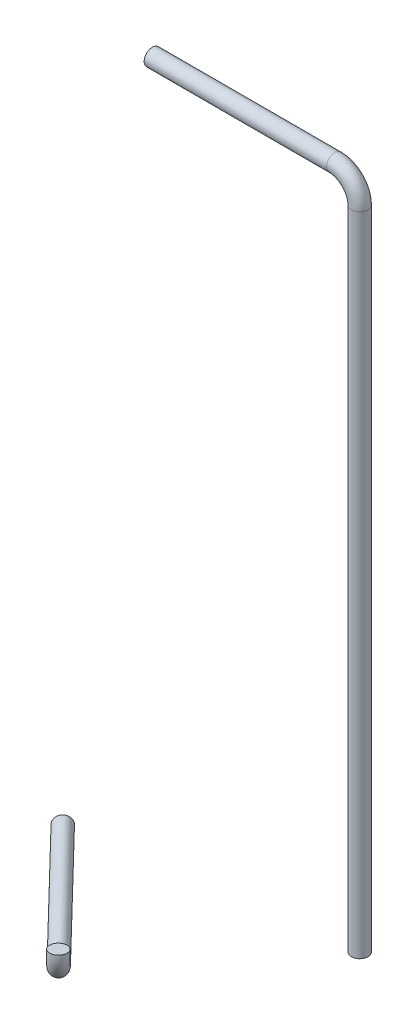
SolidWorks part; units mm, degrees
ref_plane "Front Plane" through (0, 0, 0) normal (0, 0, 1) x (1, 0, 0)
ref_plane "Top Plane" through (0, 0, 0) normal (0, 1, 0) x (1, 0, 0)
ref_plane "Right Plane" through (0, 0, 0) normal (1, 0, 0) x (0, 0, -1)
sketch "Sketch1" plane through (0, 0, 0) normal (0, 0, 1) x (1, 0, 0)
  line L0 (0, 0) -> (22, 0)
  line L1 (25, -3) -> (25, -81.02)
  arc A0 (22, 0) -> (25, -3) centre (22, -3) cw
  point P6 (25, 0)
  dimension "D3" = 3
  dimension "D1" = 25
  dimension "D2" = 81.02
sketch "Sketch3" plane through (0, 0, 0) normal (1, 0, 0) x (0, 0, -1)
  circle A0 centre (0, 0) radius 1
  dimension "D1" = 2
sweep "Sweep1" add profiles "Sketch3" path "Sketch1"
ref_plane "Plane2" through (-3.5863, 0, 3.4697) normal (0.7187, 0, -0.6953) x (-0.6953, 0, -0.7187)
ref_axis "Axis1" through (0, 0, 0) along (1, 0, 0)
ref_plane "Plane3" through (-5.5628, 0, 5.3818) normal (0.7187, 0, -0.6953) x (-0.6953, 0, -0.7187)
sketch "Sketch4" plane through (-5.5628, 0, 5.3818) normal (0.7187, 0, -0.6953) x (-0.6953, 0, -0.7187)
  line L4 (-14.3921, -84.2524) -> (5.6079, -84.2524)
  line L6 (-18.3831, -81.02) -> (-16.3831, -81.02) construction
  arc A0 (-17.3831, -81.02) -> (-14.3921, -84.2524) centre (-14.3921, -81.2524) ccw
  dimension "D2" = 20
  dimension "D1" = 3
ref_plane "Plane5" through (-9.4621, -84.2524, 1.3514) normal (-0.6953, 0, -0.7187) x (-0.7187, 0, 0.6953)
sketch "Sketch6" plane through (-9.4621, -84.2524, 1.3514) normal (-0.6953, 0, -0.7187) x (-0.7187, 0, 0.6953)
  line L0 (0, 3.2324) -> (0, 0) construction
  circle A0 centre (0, 0) radius 1
  dimension "D1" = 2
sweep "Sweep3" add profiles "Sketch6" path "Sketch4"
